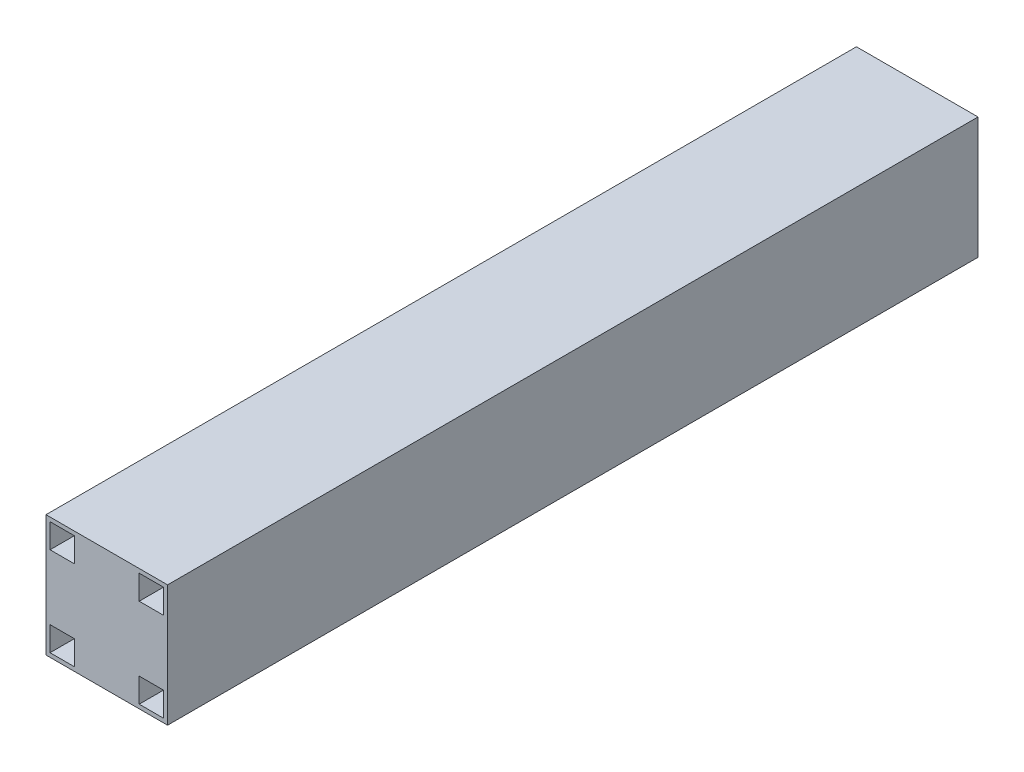
SolidWorks part; units mm, degrees
ref_plane "Front Plane" through (0, 0, 0) normal (0, 0, 1) x (1, 0, 0)
ref_plane "Top Plane" through (0, 0, 0) normal (0, 1, 0) x (1, 0, 0)
ref_plane "Right Plane" through (0, 0, 0) normal (1, 0, 0) x (0, 0, -1)
sketch "Sketch1" plane through (0, 0, 0) normal (0, 0, 1) x (1, 0, 0)
  line L0 (-43.4894, 0) -> (45.9883, 0) construction
  line L1 (0, 28.9709) -> (0, -34.4322) construction
  line L3 (-15, 15) -> (15, 15)
  line L4 (-15, 15) -> (-15, -15)
  line L5 (-15, -15) -> (15, -15)
  line L6 (15, 15) -> (15, -15)
  line L7 (-15, 15) -> (15, -15) construction
  line L8 (-15, -15) -> (15, 15) construction
  point P5 (0, 0)
  dimension "D1" = 30
  dimension "D2" = 30
extrude "Boss-Extrude1" add sketch "Sketch1" along normal blind 200
sketch "Sketch2" plane through (0, 0, 200) normal (0, 0, 1) x (1, 0, 0)
  line L0 (0, 18.2826) -> (0, -20.8625) construction
  line L1 (-20.9617, 0) -> (24.782, 0) construction
  line L2 (-20.9617, 11) -> (21.5075, 11) construction
  line L3 (-11, 19.5726) -> (-11, -20.1679) construction
  line L4 (-15, 15) -> (-15, -15) construction
  line L5 (15, 15) -> (-15, 15) construction
  line L6 (14, 8) -> (8, 8)
  line L7 (-14, 14) -> (-8, 14)
  line L8 (-14, 14) -> (-14, 8)
  line L9 (-14, 8) -> (-8, 8)
  line L10 (-8, 14) -> (-8, 8)
  line L11 (-14, 14) -> (-8, 8) construction
  line L12 (-14, 8) -> (-8, 14) construction
  line L13 (8, 14) -> (8, 8)
  line L14 (14, 14) -> (8, 14)
  line L15 (14, 14) -> (14, 8)
  line L16 (14, -14) -> (14, -8)
  line L17 (14, -14) -> (8, -14)
  line L18 (8, -14) -> (8, -8)
  line L19 (14, -8) -> (8, -8)
  line L20 (-14, -8) -> (-8, -8)
  line L21 (-8, -14) -> (-8, -8)
  line L22 (-14, -14) -> (-8, -14)
  line L23 (-14, -14) -> (-14, -8)
  point P13 (-11, 11)
  dimension "D1" = 4
  dimension "D2" = 4
  dimension "D3" = 6
  dimension "D4" = 6
extrude "Cut-Extrude1" cut sketch "Sketch2" against normal blind 200
